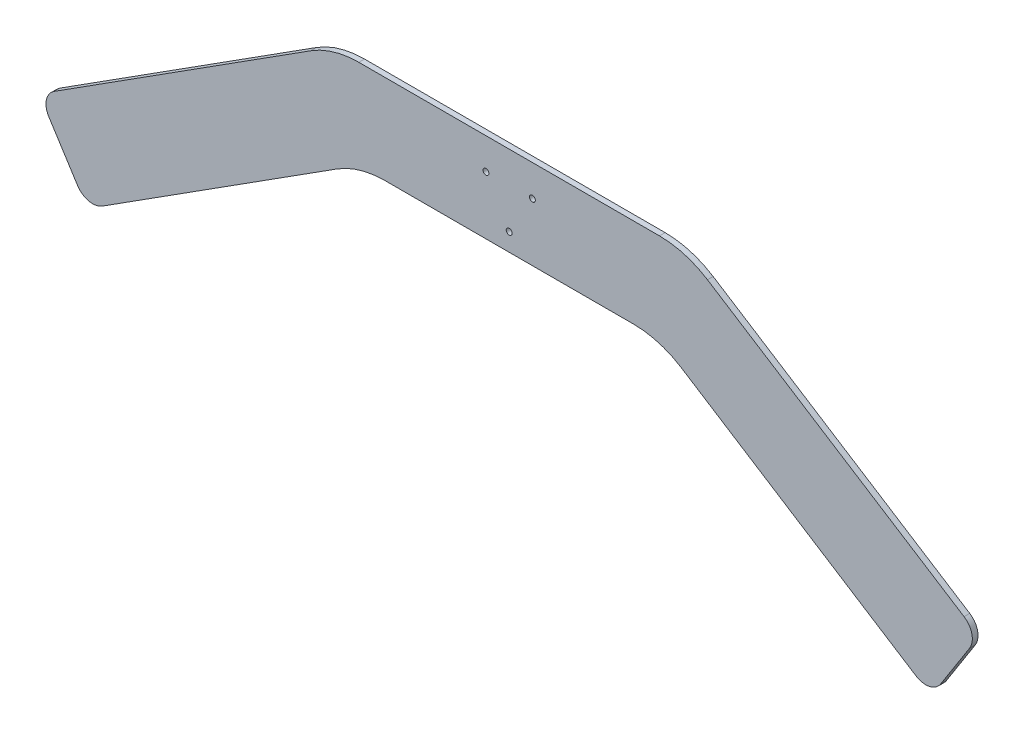
SolidWorks part; units mm, degrees
ref_plane "Front Plane" through (0, 0, 0) normal (0, 0, 1) x (1, 0, 0)
ref_plane "Top Plane" through (0, 0, 0) normal (0, 1, 0) x (1, 0, 0)
ref_plane "Right Plane" through (0, 0, 0) normal (1, 0, 0) x (0, 0, -1)
sketch "Sketch1" plane through (0, 0, 0) normal (0, 0, 1) x (1, 0, 0)
  line L0 (0, -33.2132) -> (0, -83.2132) construction
  line L1 (84.0896, -33.2132) -> (-84.0896, -33.2132)
  line L2 (-110.9546, -41.0436) -> (-262.9512, -137.8762)
  line L3 (-262.9512, -137.8762) -> (-236.0862, -180.0457)
  line L4 (-236.0862, -180.0457) -> (-96.3809, -91.0436)
  line L5 (-69.5159, -83.2132) -> (69.5159, -83.2132)
  line L6 (96.3809, -91.0436) -> (236.0862, -180.0457)
  line L7 (236.0862, -180.0457) -> (262.9512, -137.8762)
  line L8 (262.9512, -137.8762) -> (110.9546, -41.0436)
  line L9 (-98.6633, -33.2132) -> (0, 29.6422) construction
  line L10 (0, 29.6422) -> (98.6633, -33.2132) construction
  line L11 (-249.5187, -158.9609) -> (-220, -140.1555) construction
  line L12 (249.5187, -158.9609) -> (220, -140.1555) construction
  line L13 (-330, -140.1555) -> (-110, -140.1555) construction
  line L14 (-110, -140.1555) -> (110, -140.1555) construction
  line L15 (0, 0) -> (17.6777, -17.6777) construction
  line L16 (28.2843, -7.0711) -> (7.0711, -28.2843) construction
  line L17 (-7.0711, -28.2843) -> (-42.4264, 7.0711) construction
  line L18 (-42.4264, 7.0711) -> (-7.0711, 42.4264) construction
  line L19 (-7.0711, 42.4264) -> (28.2843, 7.0711) construction
  line L20 (-7.0711, 42.4264) -> (55.1264, 42.4264) construction
  circle A1 centre (0, 0) radius 7.9375 construction
  circle A2 centre (-220, -140.1555) radius 110 construction
  circle A3 centre (220, -140.1555) radius 110 construction
  arc A4 (28.2843, -7.0711) -> (28.2843, 7.0711) centre (21.2132, 0) ccw construction
  arc A5 (7.0711, -28.2843) -> (-7.0711, -28.2843) centre (0, -21.2132) cw construction
  arc A6 (69.5159, -83.2132) -> (96.3809, -91.0436) centre (69.5159, -133.2132) cw
  arc A7 (-96.3809, -91.0436) -> (-69.5159, -83.2132) centre (-69.5159, -133.2132) cw
  arc A8 (110.9546, -41.0436) -> (84.0896, -33.2132) centre (84.0896, -83.2132) ccw
  arc A9 (-84.0896, -33.2132) -> (-110.9546, -41.0436) centre (-84.0896, -83.2132) ccw
  point P2 (-54.5644, 19.209)
  point P26 (17.6777, -17.6777)
  point P33 (35.3553, 0)
  point P36 (0, -35.3553)
  point P40 (0, -31.2132)
  dimension "D1" = 50
  dimension "D2" = 15.875
  dimension "D4" = 220
  dimension "D9" = 10
  dimension "D12" = 50
  dimension "D3" = 115
  dimension "D5" = 35
  dimension "D6" = 50
  dimension "D7" = 25
  dimension "D8" = 45
  dimension "D10" = 2
  dimension "D11" = 50
extrude "Base" add sketch "Sketch1" along normal blind 3.175
fillet "Fillet1" radius 10 4 edges at (262.9512, -137.8762, 1.5875) (236.0862, -180.0457, 1.5875) (-236.0862, -180.0457, 1.5875) (-262.9512, -137.8762, 1.5875)
sketch "Sketch2" plane through (0, 0, 3.175) normal (0, 0, 1) x (1, 0, 0)
  line L0 (0, -33.2132) -> (0, -83.2132) construction
  line L1 (84.0896, -33.2132) -> (-84.0896, -33.2132) construction
  line L2 (-69.5159, -83.2132) -> (69.5159, -83.2132) construction
  circle A0 centre (0, -58.2132) radius 15 construction
  circle A1 centre (-12.9904, -50.7132) radius 1.65
  circle A2 centre (12.9904, -50.7132) radius 1.65
  circle A3 centre (0, -73.2132) radius 1.65
  point P10 (0, 0)
  point P11 (11.3322, -52.1926)
  point P12 (0, -58.2132)
  point P17 (0, -58.2132)
  dimension "D1" = 30
  dimension "D2" = 3.3
  dimension "D3" = 3
extrude "Adapter Attachment" cut sketch "Sketch2" against normal through all
